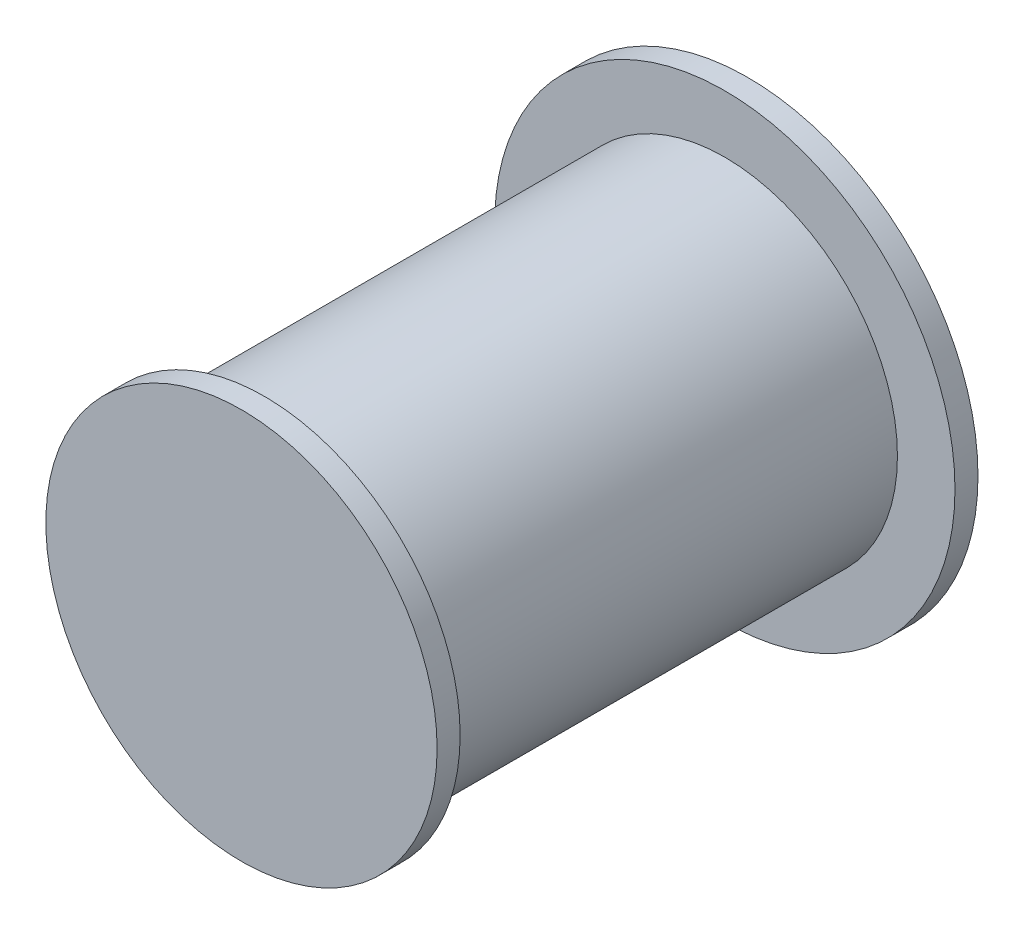
SolidWorks part; units mm, degrees
material "Acciaio al carbonio semplice"
ref_plane "Front Plane" through (0, 0, 0) normal (0, 0, 1) x (1, 0, 0)
ref_plane "Top Plane" through (0, 0, 0) normal (0, 1, 0) x (1, 0, 0)
ref_plane "Right Plane" through (0, 0, 0) normal (1, 0, 0) x (0, 0, -1)
other "Centro di massa"
sketch "Sketch1" plane through (0, 0, 0) normal (0, 0, 1) x (1, 0, 0)
  circle A0 centre (0, 0) radius 100
  dimension "D1" = 200
extrude "Boss-Extrude1" add sketch "Sketch1" along normal blind 10
sketch "Sketch2" plane through (0, 0, 10) normal (0, 0, 1) x (1, 0, 0)
  circle A0 centre (0, 0) radius 75
  dimension "D1" = 150
extrude "Boss-Extrude2" add sketch "Sketch2" along normal blind 200
sketch "Sketch3" plane through (0, 0, 210) normal (0, 0, 1) x (1, 0, 0)
  circle A2 centre (0, 0) radius 85
  circle A3 centre (0, 0) radius 85
  dimension "D1" = 10
extrude "Boss-Extrude3" add sketch "Sketch3" along normal blind 10
